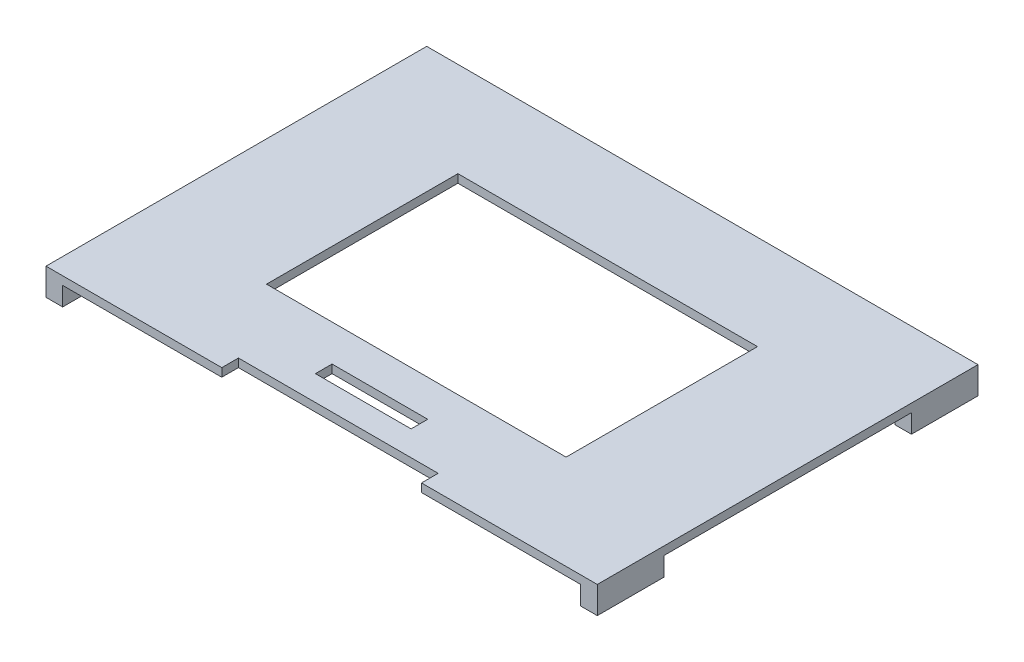
SolidWorks part; units mm, degrees
ref_plane "Front Plane" through (0, 0, 0) normal (0, 0, 1) x (1, 0, 0)
ref_plane "Top Plane" through (0, 0, 0) normal (0, 1, 0) x (1, 0, 0)
ref_plane "Right Plane" through (0, 0, 0) normal (1, 0, 0) x (0, 0, -1)
sketch "Sketch1" plane through (0, 0, 0) normal (0, 1, 0) x (1, 0, 0)
  line L1 (-210.3438, -145.2563) -> (210.3438, -145.2563)
  line L2 (-210.3438, -145.2563) -> (-210.3438, 145.2562)
  line L3 (-210.3438, 145.2562) -> (210.3438, 145.2562)
  line L4 (210.3438, -145.2563) -> (210.3438, 145.2562)
  line L5 (-210.3438, -145.2563) -> (210.3438, 145.2562) construction
  line L6 (-210.3438, 145.2562) -> (210.3438, -145.2563) construction
  point P0 (0, 0)
  dimension "D1" = 420.6875
  dimension "D2" = 290.5125
extrude "Boss-Extrude1" add sketch "Sketch1" along normal blind 6.35
sketch "Sketch2" plane through (0, 6.35, 0) normal (0, 1, 0) x (1, 0, 0)
  line L0 (-210.3438, -145.2563) -> (210.3438, -145.2563) construction
  line L1 (-114.3, -73.025) -> (114.3, -73.025)
  line L2 (-114.3, -73.025) -> (-114.3, 73.025)
  line L3 (-114.3, 73.025) -> (114.3, 73.025)
  line L4 (114.3, -73.025) -> (114.3, 73.025)
  line L5 (-114.3, -73.025) -> (114.3, 73.025) construction
  line L6 (-114.3, 73.025) -> (114.3, -73.025) construction
  line L7 (-36.5125, -113.5063) -> (36.5125, -113.5063)
  line L8 (-36.5125, -113.5063) -> (-36.5125, -100.8063)
  line L9 (-36.5125, -100.8063) -> (36.5125, -100.8063)
  line L10 (36.5125, -113.5063) -> (36.5125, -100.8063)
  line L11 (-36.5125, -113.5063) -> (36.5125, -100.8063) construction
  line L12 (-36.5125, -100.8063) -> (36.5125, -113.5063) construction
  line L13 (-76.2, -132.5563) -> (76.2, -132.5563)
  line L14 (-76.2, -132.5563) -> (-76.2, -145.2563)
  line L15 (-76.2, -145.2563) -> (76.2, -145.2563)
  line L16 (76.2, -132.5563) -> (76.2, -145.2563)
  line L17 (-76.2, -132.5563) -> (76.2, -145.2563) construction
  line L18 (-76.2, -145.2563) -> (76.2, -132.5563) construction
  point P0 (0, 0)
  point P6 (0, -107.1563)
  point P12 (0, -138.9062)
  point P18 (0, 0)
  point P19 (0, 0)
  dimension "D1" = 228.6
  dimension "D2" = 146.05
  dimension "D3" = 73.025
  dimension "D4" = 12.7
  dimension "D5" = 38.1
  dimension "D6" = 6.35
  dimension "D7" = 152.4
extrude "Cut-Extrude1" cut sketch "Sketch2" against normal through all
sketch "Sketch4" plane through (0, 0, 0) normal (0, -1, 0) x (1, 0, 0)
  line L0 (-210.3438, -145.2562) -> (-210.3438, 145.2563) construction
  line L1 (-197.6438, 94.4563) -> (-210.3438, 94.4563)
  line L2 (-197.6438, 94.4563) -> (-197.6438, 145.2563)
  line L3 (-197.6438, 145.2563) -> (-210.3438, 145.2563)
  line L4 (-210.3438, 94.4563) -> (-210.3438, 145.2563)
  line L5 (-197.6438, 94.4563) -> (-210.3438, 145.2563) construction
  line L6 (-197.6438, 145.2563) -> (-210.3438, 94.4563) construction
  line L7 (197.6438, 94.4563) -> (210.3438, 94.4563)
  line L8 (197.6438, 94.4563) -> (197.6438, 145.2563)
  line L9 (197.6438, 145.2563) -> (210.3438, 145.2563)
  line L10 (210.3438, 94.4563) -> (210.3438, 145.2563)
  line L11 (197.6438, 94.4563) -> (210.3438, 145.2563) construction
  line L12 (197.6438, 145.2563) -> (210.3438, 94.4563) construction
  line L13 (-197.6438, -94.4562) -> (-210.3438, -94.4562)
  line L14 (-197.6438, -94.4562) -> (-197.6438, -145.2562)
  line L15 (-197.6438, -145.2562) -> (-210.3438, -145.2562)
  line L16 (-210.3438, -94.4562) -> (-210.3438, -145.2562)
  line L17 (-197.6438, -94.4562) -> (-210.3438, -145.2562) construction
  line L18 (-197.6438, -145.2562) -> (-210.3438, -94.4562) construction
  line L19 (210.3438, 145.2563) -> (210.3438, -145.2562) construction
  line L20 (197.6438, -94.4562) -> (210.3438, -94.4562)
  line L21 (197.6438, -94.4562) -> (197.6438, -145.2562)
  line L22 (197.6438, -145.2562) -> (210.3438, -145.2562)
  line L23 (210.3438, -94.4562) -> (210.3438, -145.2562)
  line L24 (197.6438, -94.4562) -> (210.3438, -145.2562) construction
  line L25 (197.6438, -145.2562) -> (210.3438, -94.4562) construction
  point P0 (-203.9938, 119.8563)
  point P6 (203.9938, 119.8563)
  point P12 (-203.9938, -119.8562)
  point P19 (203.9938, -119.8562)
  dimension "D1" = 12.7
  dimension "D2" = 50.8
  dimension "D3" = 12.7
  dimension "D4" = 50.8
  dimension "D5" = 12.7
  dimension "D6" = 50.8
  dimension "D7" = 12.7
  dimension "D8" = 50.8
extrude "Boss-Extrude2" add sketch "Sketch4" along normal blind 14.2875
